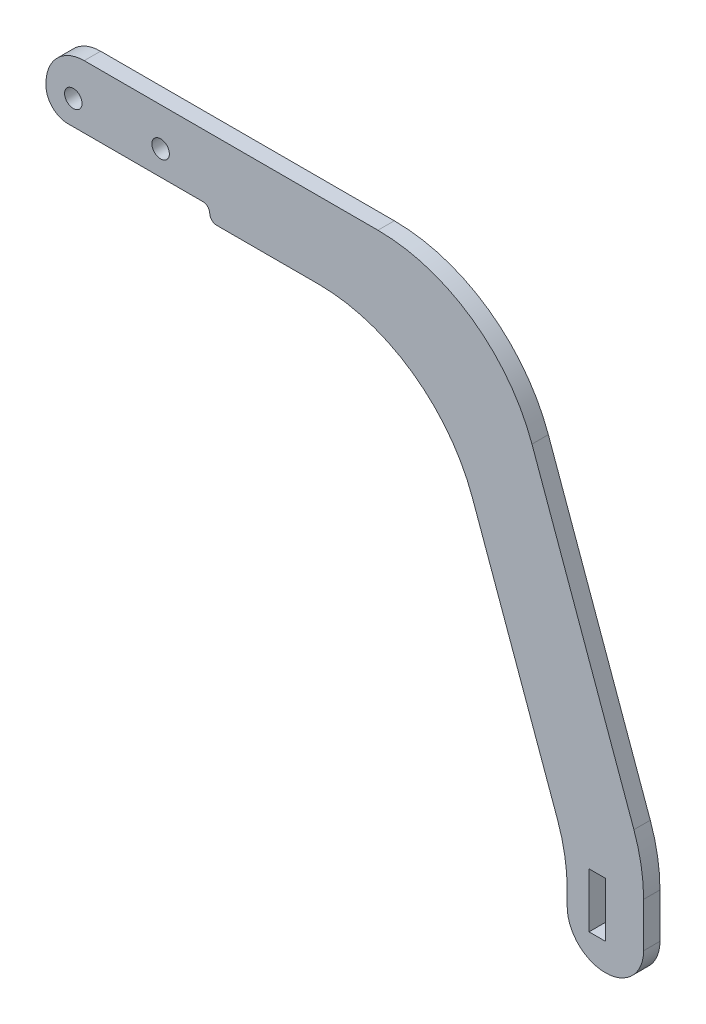
SolidWorks part; units mm, degrees
material "MDF"
ref_plane "Plano frontal" through (0, 0, 0) normal (0, 0, 1) x (1, 0, 0)
ref_plane "Plano superior" through (0, 0, 0) normal (0, 1, 0) x (1, 0, 0)
ref_plane "Plano direito" through (0, 0, 0) normal (1, 0, 0) x (0, 0, -1)
sketch "Esboço1" plane through (0, 0, 0) normal (0, 0, 1) x (1, 0, 0)
  line L0 (0, 0) -> (0, 14)
  line L1 (0, 14) -> (81.8998, 14)
  line L2 (81.8998, 14) -> (109.5, -62.6047)
  line L3 (109.5, -62.6047) -> (109.5, -83)
  line L4 (109.5, -83) -> (95.5, -83)
  line L5 (95.5, -83) -> (95.5, -68)
  line L6 (95.5, -68) -> (71, 0)
  line L7 (71, 0) -> (0, 0)
  line L8 (5, 7) -> (21, 7) construction
  line L9 (0, 2.5) -> (30, 2.5)
  line L10 (99.5, -78) -> (102.5, -78)
  line L11 (99.5, -78) -> (99.5, -68)
  line L12 (99.5, -68) -> (102.5, -68)
  line L13 (102.5, -78) -> (102.5, -68)
  line L14 (99.5, -78) -> (102.5, -68) construction
  line L15 (99.5, -68) -> (102.5, -78) construction
  line L16 (30, 2.5) -> (30, 0)
  circle A0 centre (5, 7) radius 1.6
  circle A1 centre (21, 7) radius 1.6
  point P15 (101, -78)
  point P17 (0, 7)
  point P18 (101, -73)
  dimension "D1" = 3.2
  dimension "D2" = 7
  dimension "D3" = 16
  dimension "D4" = 5
  dimension "D5" = 15
  dimension "D6" = 3
  dimension "D7" = 10
  dimension "D8" = 5
  dimension "D9" = 7
  dimension "D10" = 4
  dimension "D11" = 50
  dimension "D12" = 85
  dimension "D13" = 80
  dimension "D14" = 15
  dimension "D15" = 2.5
  dimension "D16" = 30
extrude "Ressalto-extrusão1" add sketch "Esboço1" along normal blind 3 contours L9 L16 L7 L6 L5 L4 L3 L2 L1 L0 A1 A0 L13 L10 L11 L12 region at (1.4628, 8.25, 0)
fillet "Filete3" radius 30 4 edges at (95.5, -68, 1.5) (109.5, -62.6047, 1.5) (81.8998, 14, 1.5) (71, 0, 1.5)
fillet "Filete4" radius 7 3 edges at (0, 14, 1.5) (109.5, -83, 1.5) (95.5, -83, 1.5)
fillet "Filete5" radius 1.25 2 edges at (30, 0, 1.5) (30, 2.5, 1.5)
fillet "3" radius 4 1 edges at (0, 2.5, 1.5)
